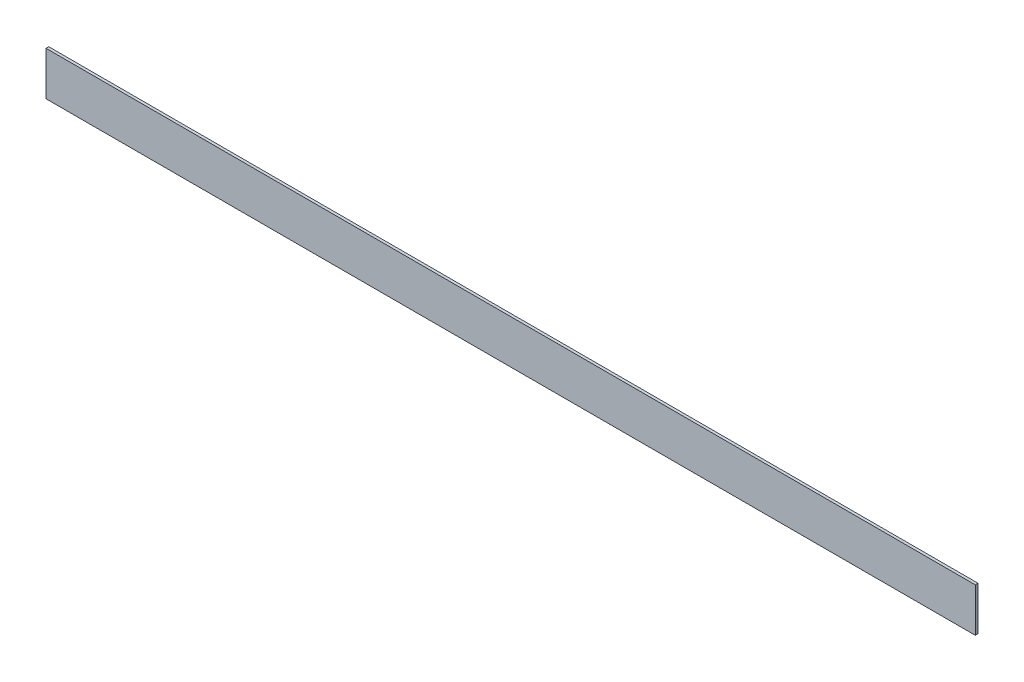
SolidWorks part; units mm, degrees
ref_plane "Front Plane" through (0, 0, 0) normal (0, 0, 1) x (1, 0, 0)
ref_plane "Top Plane" through (0, 0, 0) normal (0, 1, 0) x (1, 0, 0)
ref_plane "Right Plane" through (0, 0, 0) normal (1, 0, 0) x (0, 0, -1)
sketch "Sketch1" plane through (0, 0, 0) normal (0, 0, 1) x (1, 0, 0)
  line L1 (0, 0) -> (539.75, 0)
  line L2 (0, 0) -> (0, 25.4)
  line L3 (0, 25.4) -> (539.75, 25.4)
  line L4 (539.75, 0) -> (539.75, 25.4)
  dimension "D1" = 25.4
  dimension "D2" = 539.75
extrude "Boss-Extrude1" add sketch "Sketch1" along normal blind 1.5875
